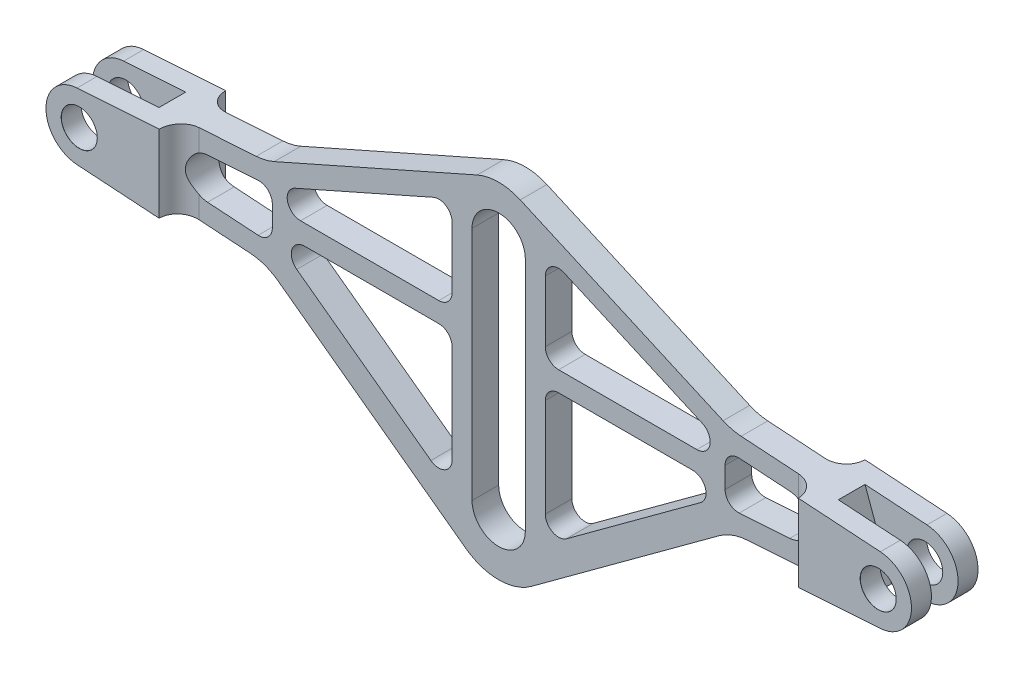
SolidWorks part; units mm, degrees
material "1060 Alloy"
ref_plane "Front Plane" through (0, 0, 0) normal (0, 0, 1) x (1, 0, 0)
ref_plane "Top Plane" through (0, 0, 0) normal (0, 1, 0) x (1, 0, 0)
ref_plane "Right Plane" through (0, 0, 0) normal (1, 0, 0) x (0, 0, -1)
sketch "Sketch1" plane through (0, 0, 0) normal (0, 0, 1) x (1, 0, 0)
  line L0 (-150, 0) -> (150, 0) construction
  line L1 (0, -55) -> (0, 33.5) construction
  line L2 (-150.8175, 12.4732) -> (-87.5, 16.6233)
  line L3 (-87.5, 16.6233) -> (-8.0986, 51.787)
  line L4 (-150.8175, -12.4732) -> (-87.5, -16.6233)
  line L5 (-87.5, -16.6233) -> (-12.3101, -71.7809)
  line L6 (87.5, -16.6233) -> (12.3101, -71.7809)
  line L7 (150.8175, -12.4732) -> (87.5, -16.6233)
  line L8 (150.8175, 12.4732) -> (87.5, 16.6233)
  line L9 (87.5, 16.6233) -> (8.0986, 51.787)
  arc A0 (8.0986, 51.787) -> (-8.0986, 51.787) centre (0, 33.5) ccw
  arc A1 (-12.3101, -71.7809) -> (12.3101, -71.7809) centre (0, -55) ccw
  arc A2 (-150.8175, 12.4732) -> (-150.8175, -12.4732) centre (-150, 0) ccw
  arc A3 (150.8175, -12.4732) -> (150.8175, 12.4732) centre (150, 0) ccw
  point P3 (0, 0)
  point P4 (0, 0)
  point P10 (0, 0)
  dimension "D4" = 40
  dimension "D5" = 25
  dimension "D8" = 20.812
  dimension "D1" = 300
  dimension "D2" = 33.5
  dimension "D3" = 88.5
  dimension "D6" = 7.5
  dimension "D7" = 175
extrude "Boss-Extrude1" add sketch "Sketch1" along normal mid plane 25 contours L2 L3 A0 L9 L8 A3 L7 L6 A1 L5 L4 A2
sketch "Sketch2" plane through (0, 0, 12.5) normal (0, 0, 1) x (1, 0, 0)
  line L1 (-120, -90.8294) -> (120, -90.8294)
  line L2 (-120, -90.8294) -> (-120, 90.8294)
  line L3 (-120, 90.8294) -> (120, 90.8294)
  line L4 (120, -90.8294) -> (120, 90.8294)
  line L5 (-120, -90.8294) -> (120, 90.8294) construction
  line L6 (-120, 90.8294) -> (120, -90.8294) construction
  point P0 (0, 0)
  dimension "D1" = 240
extrude "Cut-Extrude1" cut sketch "Sketch2" against normal offset from surface (7.5 mm away) 5 up to plane "Front Plane"
mirror "Mirror2" about plane through (0, 0, 0) normal (0, 0, 1) of "Cut-Extrude1"
sketch "Sketch3" plane through (0, 0, 12.5) normal (0, 0, 1) x (1, 0, 0)
  point P0 (-150, 0)
  point P3 (150, 0)
hole_wizard "Ø13.5 (13.5) Diameter Hole1" positions "Sketch3" profile "Sketch4" hole size "Ø13.5" standard "ANSI Metric" end condition through all
sketch "Sketch4" plane through (-150, 0, 12.5) normal (1, 0, 0) x (0, -1, 0)
  line L0 (0, 0) -> (0, 25)
  line L1 (0, 25) -> (6.75, 25)
  line L2 (6.75, 25) -> (6.75, 0.025)
  line L3 (6.75, 0.025) -> (6.775, 0)
  line L5 (6.775, 0) -> (0, 0)
  line L6 (-6.75, 0.025) -> (-6.775, 0) construction
  line L11 (0, -6.35) -> (0, 107.95) construction
  dimension "Thru Hole Dia." = 13.5
  dimension "Thru Hole Depth" = 25
  dimension "Near C'Sink Dia." = 13.55
  dimension "Near C'Sink Angle" = 90
sketch "Sketch5" plane through (0, 0, 0) normal (0, 0, 1) x (1, 0, 0)
  line L0 (-137.5, -13.3461) -> (-127.5474, 13.9984)
  line L1 (-150.8175, -12.4732) -> (-120, -14.4931) construction
  line L2 (-150.8175, 12.4732) -> (-120, 14.4931) construction
  line L3 (-150, 0) -> (-150, 19.4664) construction
  line L6 (-120, -14.4931) -> (-120, 14.4931)
  line L7 (-120, 14.4931) -> (-150.8175, 12.4732)
  line L8 (-150.8175, -12.4732) -> (-120, -14.4931)
  line L10 (-127.5474, 13.9984) -> (-150.8175, 12.4732)
  line L11 (-150.8175, -12.4732) -> (-137.5, -13.3461)
  arc A1 (-150.8175, 12.4732) -> (-150.8175, -12.4732) centre (-150, 0) ccw
  arc A2 (-150.8175, 12.4732) -> (-150.8175, -12.4732) centre (-150, 0) ccw
  dimension "D2" = 12.5
  dimension "D3" = 20
  dimension "D1" = 0
extrude "Cut-Extrude2" cut sketch "Sketch5" against normal mid plane 10
mirror "Mirror3" about plane through (0, 0, 0) normal (1, 0, 0) of "Cut-Extrude2"
fillet "Fillet1" radius 7.5 4 edges at (120, 0, -5) (120, 0, 5) (-120, 0, -5) (-120, 0, 5)
fillet "Fillet2" radius 20 4 edges at (87.5, 16.6233, 0) (87.5, -16.6233, 0) (-87.5, -16.6233, 0) (-87.5, 16.6233, 0)
sketch "Sketch6" plane through (0, 0, 5) normal (0, 0, 1) x (1, 0, 0)
  line L0 (0, 33.5) -> (0, -55) construction
  line L1 (10, 33.5) -> (10, -55)
  line L2 (-10, 33.5) -> (-10, -55)
  arc A0 (10, 33.5) -> (-10, 33.5) centre (0, 33.5) ccw
  arc A1 (-10, -55) -> (10, -55) centre (0, -55) ccw
  point P3 (0, -10.75)
  point P8 (0, 33.5)
  point P9 (0, -55)
  dimension "D1" = 20
extrude "Cut-Extrude3" cut sketch "Sketch6" against normal through all
sketch "Sketch7" plane through (0, 0, 5) normal (0, 0, 1) x (1, 0, 0)
  line L2 (81.2161, 11.2036) -> (5.0616, 44.9294)
  line L3 (76.4332, 13.3217) -> (24.5246, 36.31)
  line L5 (17.5, -55) -> (17.5, 33.5)
  line L6 (17.5, 8.75) -> (17.5, 31.7382)
  line L7 (0, 0) -> (105.202, 0) construction
  line L8 (76.8827, -12.0097) -> (6.3952, -63.7178)
  line L9 (75.8306, -12.7816) -> (25.4575, -49.7342)
  line L10 (22.5, -3.75) -> (72.8731, -3.75)
  line L11 (22.5, 3.75) -> (74.4086, 3.75)
  line L12 (0, 3.75) -> (105.202, 3.75) construction
  line L14 (17.5, -8.75) -> (17.5, -45.7026)
  line L15 (0, -3.75) -> (105.202, -3.75) construction
  arc A0 (24.5246, 36.31) -> (17.5, 31.7382) centre (22.5, 31.7382) ccw
  arc A1 (74.4086, 3.75) -> (76.4332, 13.3217) centre (74.4086, 8.75) ccw
  arc A2 (22.5, 3.75) -> (17.5, 8.75) centre (22.5, 8.75) cw
  arc A3 (25.4575, -49.7342) -> (17.5, -45.7026) centre (22.5, -45.7026) cw
  arc A4 (22.5, -3.75) -> (17.5, -8.75) centre (22.5, -8.75) ccw
  arc A5 (72.8731, -3.75) -> (75.8306, -12.7816) centre (72.8731, -8.75) cw
  dimension "D6" = 5
  dimension "D7" = 5
  dimension "D8" = 5
  dimension "D9" = 5
  dimension "D10" = 5
  dimension "D11" = 5
  dimension "D1" = 7.5
  dimension "D2" = 7.5
  dimension "D3" = 10
  dimension "D4" = 3.75
  dimension "D5" = 3.75
extrude "Cut-Extrude4" cut sketch "Sketch7" against normal through all
mirror "Mirror4" about plane through (0, 0, 0) normal (1, 0, 0) of "Cut-Extrude4"
sketch "Sketch8" plane through (0, 0, 5) normal (0, 0, 1) x (1, 0, 0)
  line L2 (-112.0095, 7.5008) -> (-90.553, 8.9071)
  line L3 (-109.309, 7.6778) -> (-90.327, 8.9219)
  line L4 (-85, 3.9326) -> (-85, -3.9326)
  line L5 (-112.0095, -7.5008) -> (-92.8289, -8.7579)
  line L6 (-109.309, -7.6778) -> (-90.327, -8.9219)
  line L8 (0, 0) -> (0, 35.6762) construction
  arc A1 (-85, 3.9326) -> (-90.327, 8.9219) centre (-90, 3.9326) ccw
  arc A2 (-85, -3.9326) -> (-90.327, -8.9219) centre (-90, -3.9326) cw
  arc A3 (-109.309, 7.6778) -> (-109.309, -7.6778) centre (-108.8058, 0) ccw
  dimension "D3" = 5
  dimension "D4" = 5
  dimension "D5" = 31.5
  dimension "D6" = 170
  dimension "D1" = 7.5
  dimension "D2" = 7.5
extrude "Cut-Extrude5" cut sketch "Sketch8" against normal through all both and the other way through all
mirror "Mirror5" about plane through (0, 0, 0) normal (1, 0, 0) of "Cut-Extrude5"
